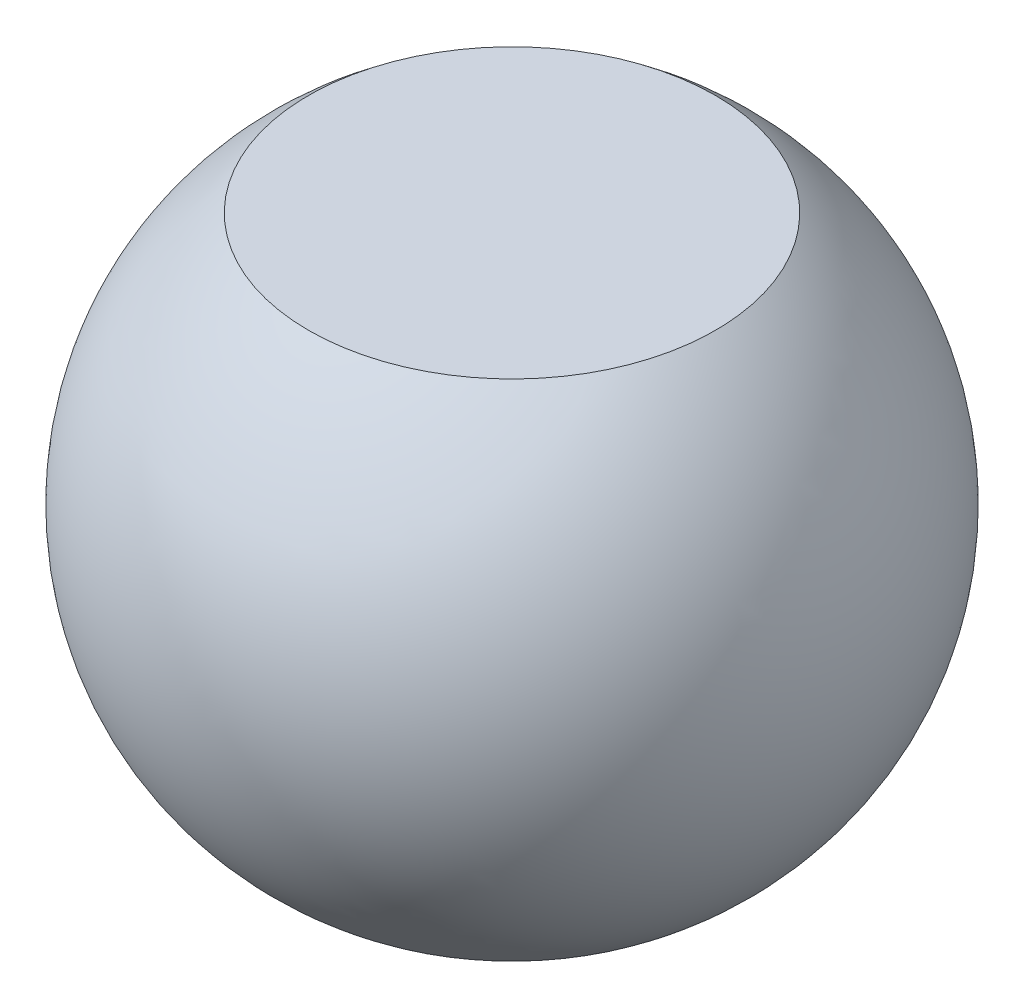
SolidWorks part; units mm, degrees
ref_plane "Front Plane" through (0, 0, 0) normal (0, 0, 1) x (1, 0, 0)
ref_plane "Top Plane" through (0, 0, 0) normal (0, 1, 0) x (1, 0, 0)
ref_plane "Right Plane" through (0, 0, 0) normal (1, 0, 0) x (0, 0, -1)
sketch "Sketch2" plane through (0, 0, 0) normal (1, 0, 0) x (0, 0, -1)
  line L0 (0, 0) -> (0, 805) construction
  line L1 (0, 0) -> (323, 0) construction
  line L2 (323, 0) -> (0, 0)
  line L3 (0, 805) -> (324.4168, 805)
  line L4 (0, 0) -> (0, 805)
  arc A0 (323, 0) -> (324.4168, 805) centre (23.7135, 403.028) ccw
  dimension "D3" = 502
  dimension "D1" = 323
  dimension "D2" = 805
revolve "Revolve1" add sketch "Sketch2" angle 360 about L4
sketch "Sketch3" plane through (0, 0, 0) normal (0, 0, 1) x (1, 0, 0)
  line L0 (-893, 784) -> (-745.515, 820.7721)
  line L1 (-893, 784) -> (-703.8317, 784) construction
  line L2 (-124.0567, 112.3589) -> (-741.9433, 112.3589) construction
  line L3 (-535.9692, 694.9822) -> (-1250.0308, 873.0178) construction
  line L4 (-71.2089, 479.0122) -> (-933.1057, 630.9878) construction
  line L5 (-450.0948, 525.3518) -> (-1040.9353, 1116.1924) construction
  arc A0 (-502.1573, 555) -> (-433, 112.3589) centre (-23.7135, 403.028) ccw
  arc A1 (-324.4168, 805) -> (-323, 0) centre (-23.7135, 403.028) ccw construction
  spline S0 degree 3 poles (-893, 784) (-661.7462, 726.3419) (-757, 112.3589) (-433, 112.3589) knots 0 0 0 0 1 1 1 1
  spline S1 degree 3 poles (-745.515, 820.7721) (-647.0416, 722.2987) (-645.8068, 580.3293) (-502.1573, 555) knots 0 0 0 0 1 1 1 1
  dimension "D7" = 972
  dimension "D8" = 14
  dimension "D9" = 715
  dimension "D10" = 10
  dimension "D11" = 45
  dimension "D1" = 433
  dimension "D2" = 555
  dimension "D3" = 152
  dimension "D4" = 14
  dimension "D5" = 784
  dimension "D6" = 893
